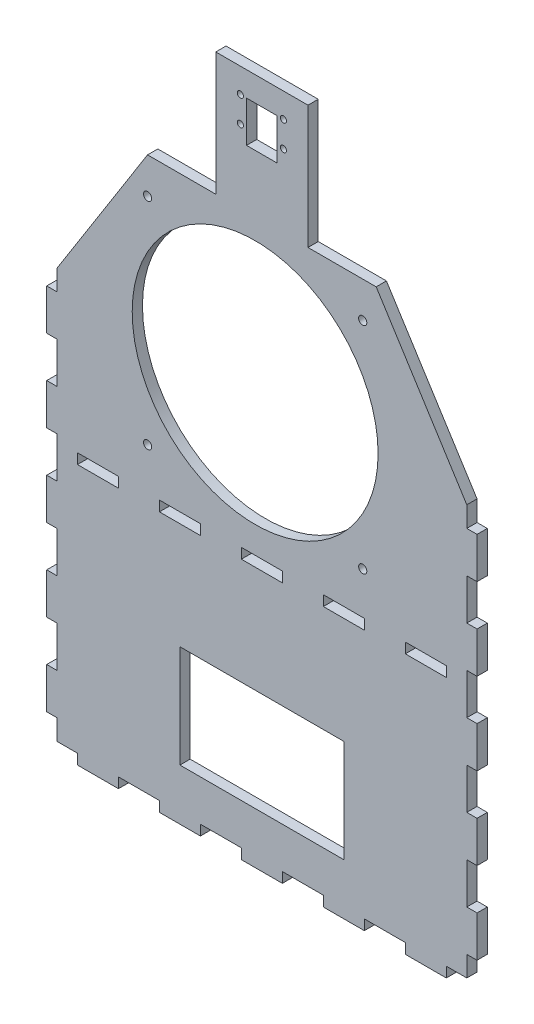
SolidWorks part; units mm, degrees
ref_plane "Přední rovina" through (0, 0, 0) normal (0, 0, 1) x (1, 0, 0)
ref_plane "Horní rovina" through (0, 0, 0) normal (0, 1, 0) x (1, 0, 0)
ref_plane "Pravá rovina" through (0, 0, 0) normal (1, 0, 0) x (0, 0, -1)
sketch "Skica1" plane through (0, 0, 0) normal (0, 0, 1) x (1, 0, 0)
  line L0 (-21.5981, -113.24) -> (-21.5981, -95.4761)
  line L1 (-121.5981, -113.24) -> (78.4019, -113.24)
  line L2 (-121.5981, -113.24) -> (-121.5981, 156.76)
  line L3 (-121.5981, 156.76) -> (78.4019, 156.76)
  line L4 (78.4019, -113.24) -> (78.4019, 156.76)
  line L5 (-111.5981, -113.24) -> (-91.5981, -113.24)
  line L6 (-111.5981, -113.24) -> (-111.5981, -118.24)
  line L7 (-111.5981, -118.24) -> (-91.5981, -118.24)
  line L8 (-91.5981, -113.24) -> (-91.5981, -118.24)
  line L9 (-71.5981, -113.24) -> (-51.5981, -113.24)
  line L10 (-71.5981, -113.24) -> (-71.5981, -118.24)
  line L11 (-71.5981, -118.24) -> (-51.5981, -118.24)
  line L12 (-51.5981, -113.24) -> (-51.5981, -118.24)
  line L13 (-31.5981, -113.24) -> (-11.5981, -113.24)
  line L14 (-31.5981, -113.24) -> (-31.5981, -118.24)
  line L15 (-31.5981, -118.24) -> (-11.5981, -118.24)
  line L16 (-11.5981, -113.24) -> (-11.5981, -118.24)
  line L17 (28.4019, -118.24) -> (8.4019, -118.24)
  line L18 (8.4019, -113.24) -> (8.4019, -118.24)
  line L19 (28.4019, -113.24) -> (8.4019, -113.24)
  line L20 (28.4019, -113.24) -> (28.4019, -118.24)
  line L21 (68.4019, -118.24) -> (48.4019, -118.24)
  line L22 (48.4019, -113.24) -> (48.4019, -118.24)
  line L23 (68.4019, -113.24) -> (48.4019, -113.24)
  line L24 (68.4019, -113.24) -> (68.4019, -118.24)
  line L25 (78.4019, 36.76) -> (83.4019, 36.76)
  line L26 (-121.5981, -103.24) -> (-126.5981, -103.24)
  line L27 (-121.5981, -103.24) -> (-121.5981, -83.24)
  line L28 (-121.5981, -83.24) -> (-126.5981, -83.24)
  line L29 (-126.5981, -103.24) -> (-126.5981, -83.24)
  line L30 (-121.5981, -63.24) -> (-126.5981, -63.24)
  line L31 (-121.5981, -63.24) -> (-121.5981, -43.24)
  line L32 (-121.5981, -43.24) -> (-126.5981, -43.24)
  line L33 (-126.5981, -63.24) -> (-126.5981, -43.24)
  line L34 (-121.5981, -23.24) -> (-126.5981, -23.24)
  line L35 (-121.5981, -23.24) -> (-121.5981, -3.24)
  line L36 (-121.5981, -3.24) -> (-126.5981, -3.24)
  line L37 (-126.5981, -23.24) -> (-126.5981, -3.24)
  line L38 (-121.5981, 16.76) -> (-126.5981, 16.76)
  line L39 (-121.5981, 16.76) -> (-121.5981, 36.76)
  line L40 (-121.5981, 36.76) -> (-126.5981, 36.76)
  line L41 (-126.5981, 16.76) -> (-126.5981, 36.76)
  line L42 (83.4019, 16.76) -> (83.4019, 36.76)
  line L43 (78.4019, 16.76) -> (83.4019, 16.76)
  line L44 (78.4019, 16.76) -> (78.4019, 36.76)
  line L45 (78.4019, -3.24) -> (83.4019, -3.24)
  line L46 (83.4019, -23.24) -> (83.4019, -3.24)
  line L47 (78.4019, -23.24) -> (83.4019, -23.24)
  line L48 (78.4019, -23.24) -> (78.4019, -3.24)
  line L49 (78.4019, -43.24) -> (83.4019, -43.24)
  line L50 (83.4019, -63.24) -> (83.4019, -43.24)
  line L51 (78.4019, -63.24) -> (83.4019, -63.24)
  line L52 (78.4019, -63.24) -> (78.4019, -43.24)
  line L53 (78.4019, -83.24) -> (83.4019, -83.24)
  line L54 (83.4019, -103.24) -> (83.4019, -83.24)
  line L55 (78.4019, -103.24) -> (83.4019, -103.24)
  line L56 (78.4019, -103.24) -> (78.4019, -83.24)
  line L57 (-77.3799, 156.76) -> (-121.5981, 86.76)
  line L58 (-111.5981, 13.76) -> (-91.5981, 13.76)
  line L59 (-111.5981, 13.76) -> (-111.5981, 8.76)
  line L60 (-111.5981, 8.76) -> (-91.5981, 8.76)
  line L61 (-91.5981, 13.76) -> (-91.5981, 8.76)
  line L62 (-71.5981, 13.76) -> (-51.5981, 13.76)
  line L63 (-71.5981, 13.76) -> (-71.5981, 8.76)
  line L64 (-71.5981, 8.76) -> (-51.5981, 8.76)
  line L65 (-51.5981, 13.76) -> (-51.5981, 8.76)
  line L66 (-31.5981, 13.76) -> (-11.5981, 13.76)
  line L67 (-31.5981, 13.76) -> (-31.5981, 8.76)
  line L68 (-31.5981, 8.76) -> (-11.5981, 8.76)
  line L69 (-11.5981, 13.76) -> (-11.5981, 8.76)
  line L70 (8.4019, 13.76) -> (28.4019, 13.76)
  line L71 (8.4019, 13.76) -> (8.4019, 8.76)
  line L72 (8.4019, 8.76) -> (28.4019, 8.76)
  line L73 (28.4019, 13.76) -> (28.4019, 8.76)
  line L74 (48.4019, 13.76) -> (68.4019, 13.76)
  line L75 (48.4019, 13.76) -> (48.4019, 8.76)
  line L76 (48.4019, 8.76) -> (68.4019, 8.76)
  line L77 (68.4019, 13.76) -> (68.4019, 8.76)
  line L78 (-121.5981, 56.76) -> (-126.5981, 56.76)
  line L79 (-121.5981, 56.76) -> (-121.5981, 76.76)
  line L80 (-121.5981, 76.76) -> (-126.5981, 76.76)
  line L81 (-126.5981, 56.76) -> (-126.5981, 76.76)
  line L82 (34.1836, 156.76) -> (78.4019, 86.76)
  line L83 (78.4019, 76.76) -> (83.4019, 76.76)
  line L84 (83.4019, 56.76) -> (83.4019, 76.76)
  line L85 (78.4019, 56.76) -> (83.4019, 56.76)
  line L86 (78.4019, 56.76) -> (78.4019, 76.76)
  line L88 (-44.0981, 156.76) -> (0.9019, 156.76)
  line L89 (-44.0981, 156.76) -> (-44.0981, 216.8991)
  line L90 (-44.0981, 216.8991) -> (0.9019, 216.8991)
  line L91 (0.9019, 156.76) -> (0.9019, 216.8991)
  line L92 (-29.0981, 204.8991) -> (-14.0981, 204.8991)
  line L93 (-29.0981, 204.8991) -> (-29.0981, 184.8991)
  line L94 (-29.0981, 184.8991) -> (-14.0981, 184.8991)
  line L95 (-14.0981, 204.8991) -> (-14.0981, 184.8991)
  line L96 (-61.5981, -93.24) -> (18.4019, -93.24)
  line L97 (-61.5981, -93.24) -> (-61.5981, -43.24)
  line L98 (-61.5981, -43.24) -> (18.4019, -43.24)
  line L99 (18.4019, -93.24) -> (18.4019, -43.24)
  circle A0 centre (-24.8799, 86.76) radius 60
  circle A1 centre (-77.3799, 139.26) radius 2
  circle A2 centre (27.6201, 139.26) radius 2
  circle A3 centre (27.6201, 34.26) radius 2
  circle A4 centre (-77.3799, 34.26) radius 2
  circle A5 centre (-32.0981, 204.8991) radius 1.5
  circle A6 centre (-11.0981, 204.8991) radius 1.5
  circle A7 centre (-11.0981, 192.3991) radius 1.5
  circle A8 centre (-32.0981, 192.3991) radius 1.5
  point P89 (-121.5981, 86.76)
  point P93 (-77.3799, 156.76)
  dimension "D3" = 120
  dimension "D4" = 70
  dimension "D6" = 4
  dimension "D7" = 4
  dimension "D8" = 4
  dimension "D9" = 4
  dimension "D35" = 3
  dimension "D36" = 3
  dimension "D37" = 3
  dimension "D38" = 3
  dimension "D1" = 270
  dimension "D2" = 200
  dimension "D5" = 105
  dimension "D10" = 105
  dimension "D11" = 52.5
  dimension "D12" = 52.5
  dimension "D13" = 20
  dimension "D14" = 20
  dimension "D15" = 20
  dimension "D16" = 20
  dimension "D17" = 10
  dimension "D18" = 20
  dimension "D19" = 5
  dimension "D20" = 10
  dimension "D21" = 20
  dimension "D22" = 20
  dimension "D23" = 20
  dimension "D24" = 20
  dimension "D25" = 20
  dimension "D26" = 20
  dimension "D27" = 20
  dimension "D28" = 5
  dimension "D29" = 5
  dimension "D30" = 20
  dimension "D31" = 20
  dimension "D32" = 10
  dimension "D33" = 3
  dimension "D34" = 45
  dimension "D39" = 12.5
  dimension "D40" = 21
  dimension "D41" = 12
  dimension "D42" = 12
  dimension "D43" = 12
  dimension "D44" = 15
  dimension "D45" = 3
  dimension "D46" = 20
  dimension "D47" = 22.5
  dimension "D48" = 50
  dimension "D49" = 80
  dimension "D50" = 20
  dimension "D51" = 40
  dimension "D52" = 10
extrude "Přidat vysunutím1" add sketch "Skica1" along normal blind 5 contours L8 L1 L6 L7 | L41 L38 L2 L40 | L37 L34 L2 L36 | L1 L4 L3 L2 A4 A3 A2 A1 A0 L58 L61 L60 L59 L62 L65 | L42 L25 L44 L43 | L46 L45 L48 L47 | L50 L49 L52 L51 | L54 L53 L56 L55 | L21 L22 L23 L24 | L17 L18 L19 L20 | L15 L16 L13 L14 | L11 L12 L9 L10 | L29 L28 L27 L26 | L33 L32 L31 L30 | L79 L78 L81 L80 | L83 L84 L85 L86 | L89 L88 L91 L90 | L93 L92 L95 L94 | A7 | A8 | A5 | A6 region at (-20.5343, 1.2493, 0) region at (-101.5981, -115.74, 0) region at (-124.0981, -13.24, 0) region at (-124.0981, 26.76, 0)
